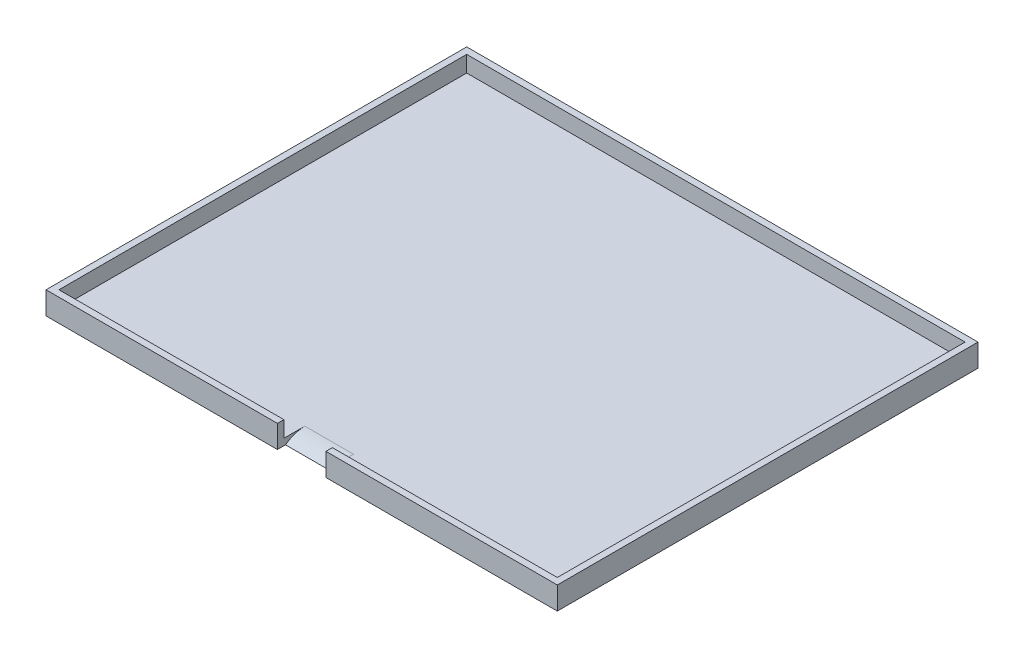
SolidWorks part; units mm, degrees
ref_plane "Plan de face" through (0, 0, 0) normal (0, 0, 1) x (1, 0, 0)
ref_plane "Plan de dessus" through (0, 0, 0) normal (0, 1, 0) x (1, 0, 0)
ref_plane "Plan de droite" through (0, 0, 0) normal (1, 0, 0) x (0, 0, -1)
sketch "Esquisse1" plane through (0, 0, 0) normal (0, 1, 0) x (1, 0, 0)
  line L1 (-39.5, 32.5) -> (39.5, 32.5)
  line L2 (-39.5, 32.5) -> (-39.5, -32.5)
  line L3 (-39.5, -32.5) -> (39.5, -32.5)
  line L4 (39.5, 32.5) -> (39.5, -32.5)
  line L5 (-39.5, 32.5) -> (39.5, -32.5) construction
  line L6 (-39.5, -32.5) -> (39.5, 32.5) construction
  point P0 (0, 0)
  dimension "D1" = 79
  dimension "D2" = 65
extrude "Boss.-Extru.1" add sketch "Esquisse1" along normal blind 3.5
sketch "Esquisse2" plane through (0, 3.5, 0) normal (0, 1, 0) x (1, 0, 0)
  line L0 (39.5, 32.5) -> (-39.5, 32.5) construction
  line L1 (38.5, -31.5) -> (-38.5, -31.5)
  line L2 (38.5, -31.5) -> (38.5, 31.5)
  line L3 (38.5, 31.5) -> (-38.5, 31.5)
  line L4 (-38.5, -31.5) -> (-38.5, 31.5)
  line L5 (38.5, -31.5) -> (-38.5, 31.5) construction
  line L6 (38.5, 31.5) -> (-38.5, -31.5) construction
  line L7 (39.5, -32.5) -> (39.5, 32.5) construction
  point P0 (0, 0)
  dimension "D1" = 1
  dimension "D2" = 1
extrude "Enlèv. mat.-Extru.1" cut sketch "Esquisse2" against normal blind 2.5
sketch "Esquisse3" plane through (0, 0, 32.5) normal (0, 0, 1) x (1, 0, 0)
  line L0 (0, 3.5) -> (0, 0) construction
  line L1 (-39.5, 3.5) -> (39.5, 3.5) construction
  line L2 (-39.5, 1.75) -> (39.5, 1.75) construction
  line L3 (-39.5, 3.5) -> (-39.5, 0) construction
  line L4 (39.5, 3.5) -> (39.5, 0) construction
  line L6 (-3.75, 5.5) -> (3.75, 5.5)
  line L7 (-3.75, 5.5) -> (-3.75, -2)
  line L8 (-3.75, -2) -> (3.75, -2)
  line L9 (3.75, 5.5) -> (3.75, -2)
  line L10 (-3.75, 5.5) -> (3.75, -2) construction
  line L11 (-3.75, -2) -> (3.75, 5.5) construction
  point P11 (0, 1.75)
  dimension "D1" = 7.5
  dimension "D2" = 7.5
extrude "Enlèv. mat.-Extru.2" cut sketch "Esquisse3" against normal blind 1.25
fillet "Congé1" radius 5 1 edges at (0, 1, 31.25)
